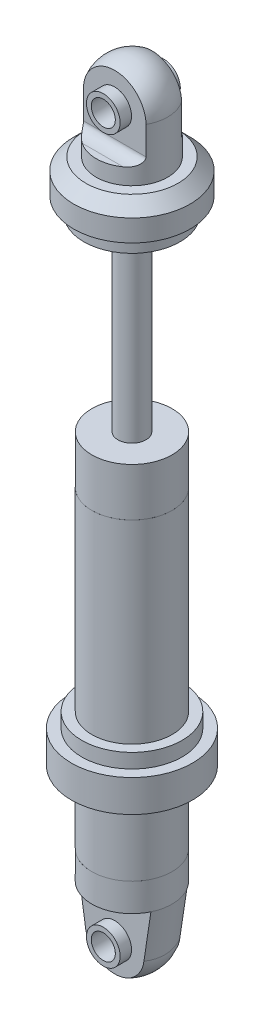
SolidWorks part; units mm, degrees
ref_plane "Front Plane" through (0, 0, 0) normal (0, 0, 1) x (1, 0, 0)
ref_plane "Top Plane" through (0, 0, 0) normal (0, 1, 0) x (1, 0, 0)
ref_plane "Right Plane" through (0, 0, 0) normal (1, 0, 0) x (0, 0, -1)
sketch "Sketch1" plane through (0, 0, 0) normal (0, 1, 0) x (1, 0, 0)
  circle A0 centre (0, 0) radius 5
  dimension "D1" = 10
extrude "Boss-Extrude1" add sketch "Sketch1" along normal blind 6
sketch "Sketch2" plane through (0, 0, 0) normal (0, -1, 0) x (1, 0, 0)
  circle A1 centre (0, 0) radius 5
  circle A2 centre (0, 0) radius 5
  dimension "D1" = 0
extrude "Boss-Extrude2" add sketch "Sketch2" along normal blind 39 separate body
sketch "Sketch3" plane through (0, -39, 0) normal (0, -1, 0) x (1, 0, 0)
  circle A1 centre (0, 0) radius 5
  circle A2 centre (0, 0) radius 5
  dimension "D1" = 0
extrude "Boss-Extrude3" add sketch "Sketch3" along normal blind 3.5 separate body
sketch "Sketch4" plane through (0, 0, 0) normal (0, 0, 1) x (1, 0, 0)
  line L0 (0, 0) -> (0, -47.8) construction
  line L1 (-5, -42.5) -> (5, -42.5)
  line L2 (5, -42.5) -> (4.0387, -48.8477)
  line L3 (-5, -42.5) -> (-4.1032, -48.4214)
  circle A0 centre (0, -47.8) radius 1.5
  circle A1 centre (0, -47.8) radius 4.15
  dimension "D2" = 8.3
  dimension "D3" = 3
  dimension "D1" = 5.3
extrude "Boss-Extrude4" add sketch "Sketch4" along normal blind 2.15 and the other way blind 2.5 contours L0 L1 L3 A1 | L1 L0 A1 L2 | A1 A0 region at (2.9845, -43.8722, 0) region at (-2.9845, -43.8722, 0) region at (2.8515, -44.9485, 0)
sketch "Sketch5" plane through (0, -42.5, 0) normal (0, -1, 0) x (1, 0, 0)
  line L0 (-4.5141, 2.15) -> (-14.8451, 2.15)
  line L1 (-4.3301, -2.5) -> (-14.7902, -2.5)
  arc A0 (4.5141, 2.15) -> (-4.5141, 2.15) centre (0, 0) ccw construction
  arc A1 (-4.5141, 2.15) -> (-4.3301, -2.5) centre (0, 0) ccw
  arc A2 (-14.8451, 2.15) -> (-14.7902, -2.5) centre (0, 0) ccw
  circle A3 centre (0, 0) radius 15 construction
  circle A4 centre (0, 0) radius 5 construction
  dimension "D1" = 10
sketch "Sketch6" plane through (0, 0, -2.5) normal (0, 0, -1) x (-1, 0, 0)
  line L0 (-5, -42.5) -> (-4.1032, -48.4214) construction
  line L1 (5, -42.5) -> (4.1032, -48.4214) construction
  line L2 (-5, -42.5) -> (-4.1032, -48.4214)
  line L3 (5, -42.5) -> (4.1032, -48.4214)
  arc A0 (-4.1032, -48.4214) -> (4.1032, -48.4214) centre (0, -47.8) ccw construction
  arc A1 (-4.1032, -48.4214) -> (4.1032, -48.4214) centre (0, -47.8) ccw
sweep "Cut-Sweep1" cut profiles "Sketch5" path "Sketch6"
sketch "Sketch7" plane through (0, 6, 0) normal (0, 1, 0) x (1, 0, 0)
  circle A0 centre (0, 0) radius 1.75
  dimension "D1" = 3.5
extrude "Boss-Extrude5" add sketch "Sketch7" along normal blind 23.5
sketch "Sketch8" plane through (0, 29.5, 0) normal (0, 1, 0) x (1, 0, 0)
  circle A0 centre (0, 0) radius 6
  dimension "D1" = 12
extrude "Boss-Extrude6" add sketch "Sketch8" along normal blind 2
sketch "Sketch9" plane through (0, 31.5, 0) normal (0, 1, 0) x (1, 0, 0)
  circle A0 centre (0, 0) radius 7.25
  dimension "D1" = 14.5
extrude "Boss-Extrude7" add sketch "Sketch9" along normal blind 4.2
sketch "Sketch10" plane through (0, 35.7, 0) normal (0, 1, 0) x (1, 0, 0)
  circle A0 centre (0, 0) radius 4.45
  dimension "D1" = 8.9
extrude "Boss-Extrude8" add sketch "Sketch10" along normal blind 2
sketch "Sketch11" plane through (0, 0, 0) normal (0, 0, 1) x (1, 0, 0)
  line L0 (0, -47.8) -> (0, 42.2) construction
  line L1 (-4.45, 42.2) -> (-4.45, 37.7)
  line L2 (-4.45, 37.7) -> (4.45, 37.7)
  line L3 (4.45, 37.7) -> (4.45, 42.2)
  circle A0 centre (0, 42.2) radius 1.5
  circle A1 centre (0, 42.2) radius 4.45
  dimension "D2" = 3
  dimension "D1" = 90
extrude "Boss-Extrude9" add sketch "Sketch11" along normal up to surface (2.15 mm away) and the other way up to surface (2.5 mm away) contours L2 L0 A1 L1 | L0 L2 L3 A1 | A1 A0 region at (-3.3948, 38.6933, 0) region at (3.3948, 38.6933, 0) region at (-3.0576, 39.1424, 0) up to face at (1.5, -47.8, 2.15) other way up to face at (1.5, -47.8, -2.5)
sketch "Sketch12" plane through (0, 37.7, 0) normal (0, 1, 0) x (1, 0, 0)
  line L4 (3.6814, 2.5) -> (12.7567, 2.5)
  line L5 (12.7567, 2.5) -> (12.7567, -2.15)
  line L6 (12.7567, -2.15) -> (3.8962, -2.15)
  arc A2 (3.8962, -2.15) -> (3.6814, 2.5) centre (0, 0) ccw
sketch "Sketch13" plane through (0, 0, 2.15) normal (0, 0, 1) x (1, 0, 0)
  line L0 (4.45, 37.7) -> (4.45, 42.2) construction
  line L1 (-4.45, 42.2) -> (-4.45, 37.7) construction
  line L2 (4.45, 37.7) -> (4.45, 42.2)
  line L3 (-4.45, 42.2) -> (-4.45, 37.7)
  arc A0 (4.45, 42.2) -> (-4.45, 42.2) centre (0, 42.2) ccw construction
  arc A1 (4.45, 42.2) -> (-4.45, 42.2) centre (0, 42.2) ccw
sweep "Cut-Sweep2" cut profiles "Sketch12" path "Sketch13"
chamfer "Chamfer1" distance 1.5 angle 45 1 edges at (0, 35.7, 7.25)
ref_plane "Plane1" through (0, -30, 0) normal (0, 1, 0) x (1, 0, 0)
sketch "Sketch14" plane through (0, -30, 0) normal (0, 1, 0) x (1, 0, 0)
  circle A0 centre (0, 0) radius 5 construction
  circle A1 centre (0, 0) radius 5
  circle A2 centre (0, 0) radius 7.55
  dimension "D1" = 15.1
extrude "Boss-Extrude10" add sketch "Sketch14" along normal blind 4 separate body
sketch "Sketch15" plane through (0, -26, 0) normal (0, 1, 0) x (1, 0, 0)
  circle A0 centre (0, 0) radius 5 construction
  circle A1 centre (0, 0) radius 5
  circle A2 centre (0, 0) radius 6.25
  dimension "D1" = 12.5
extrude "Boss-Extrude11" add sketch "Sketch15" along normal blind 1.8 separate body
combine bodies "Combine1" operation type add bodies to combine 114 113
fillet "Fillet1" radius 1.5 2 edges at (0, 37.7, 2.15) (0, 37.7, -2.5) second distance 1 first distance on face at (0, 37.7, 3.3) first distance on face at (0, 37.7, -3.475)
sketch "Sketch16" plane through (0, 0, -2.5) normal (0, 0, -1) x (-1, 0, 0)
  circle A0 centre (0, -47.8) radius 1.5 construction
  circle A1 centre (0, -47.8) radius 1.5
  circle A2 centre (0, 42.2) radius 1.5 construction
  circle A3 centre (0, 42.2) radius 1.5
  circle A4 centre (0, 42.2) radius 2.1
  circle A5 centre (0, -47.8) radius 2.1
  dimension "D1" = 4.2
extrude "Boss-Extrude12" add sketch "Sketch16" along normal blind 1.425 and the other way blind 6.075
